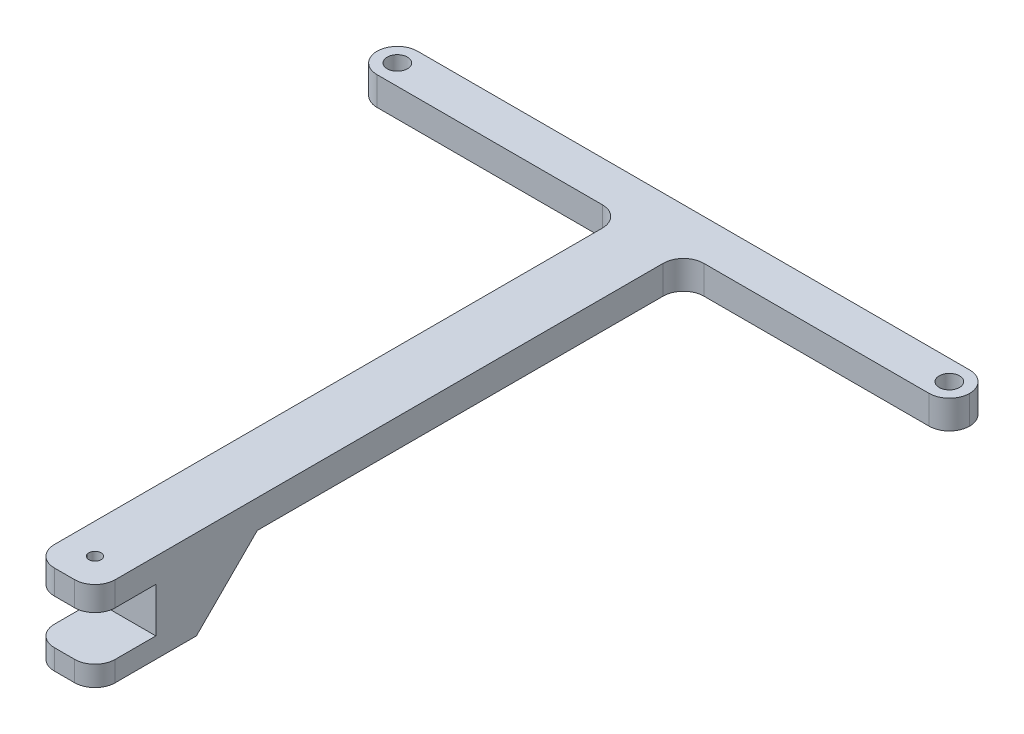
SolidWorks part; units mm, degrees
ref_plane "Alzado" through (0, 0, 0) normal (0, 0, 1) x (1, 0, 0)
ref_plane "Planta" through (0, 0, 0) normal (0, 1, 0) x (1, 0, 0)
ref_plane "Vista lateral" through (0, 0, 0) normal (1, 0, 0) x (0, 0, -1)
sketch "Croquis1" plane through (0, 0, 0) normal (1, 0, 0) x (0, 0, -1)
  line L0 (0, 0) -> (0, 11)
  line L1 (0, 11) -> (-15, 11)
  line L2 (-15, 11) -> (-15, 17)
  line L3 (-15, 17) -> (140, 17)
  line L4 (140, 17) -> (140, 10)
  line L6 (-15, -5) -> (-15, 0)
  line L7 (-15, 0) -> (0, 0)
  line L8 (-15, -5) -> (10, -5)
  line L9 (10, -5) -> (25, 10)
  line L10 (25, 10) -> (140, 10)
  dimension "D1" = 11
  dimension "D2" = 6
  dimension "D3" = 5
  dimension "D4" = 15
  dimension "D5" = 140
  dimension "D6" = 115
  dimension "D7" = 45
  dimension "D8" = 25
extrude "Saliente-Extruir1" add sketch "Croquis1" along normal mid plane 15
sketch "Croquis4" plane through (0, 17, 0) normal (0, 1, 0) x (1, 0, 0)
  line L0 (7.5, -15) -> (-7.5, -15) construction
  circle A0 centre (0, -7.5) radius 1.5
  dimension "D1" = 3
  dimension "D2" = 7.5
extrude "Cortar-Extruir2" cut sketch "Croquis4" against normal up to surface (6 mm away) up to face at (0, 11, 7.5)
sketch "Croquis5" plane through (0, 17, 0) normal (0, 1, 0) x (1, 0, 0)
  line L0 (-68, 135) -> (68, 135) construction
  line L1 (-73, 140) -> (73, 140)
  line L2 (-73, 140) -> (-73, 130)
  line L3 (-73, 130) -> (73, 130)
  line L4 (73, 140) -> (73, 130)
  line L6 (7.5, 140) -> (-7.5, 140) construction
  circle A0 centre (-68, 135) radius 2.5
  circle A1 centre (68, 135) radius 2.5
  dimension "D3" = 5
  dimension "D4" = 5
  dimension "D1" = 68
  dimension "D2" = 136
  dimension "D6" = 5
  dimension "D7" = 5
  dimension "D8" = 5
  dimension "D9" = 5
extrude "Saliente-Extruir2" add sketch "Croquis5" against normal up to surface (7 mm away) up to face at (0, 10, -82.5)
fillet "Redondeo2" radius 5 10 edges at (-7.5, 13.5, -130) (-73, 13.5, -140) (-73, 13.5, -130) (7.5, 13.5, -130) (7.5, -2.5, 15) (-7.5, -2.5, 15) (-7.5, 14, 15) (7.5, 14, 15) (73, 13.5, -140) (73, 13.5, -130)
